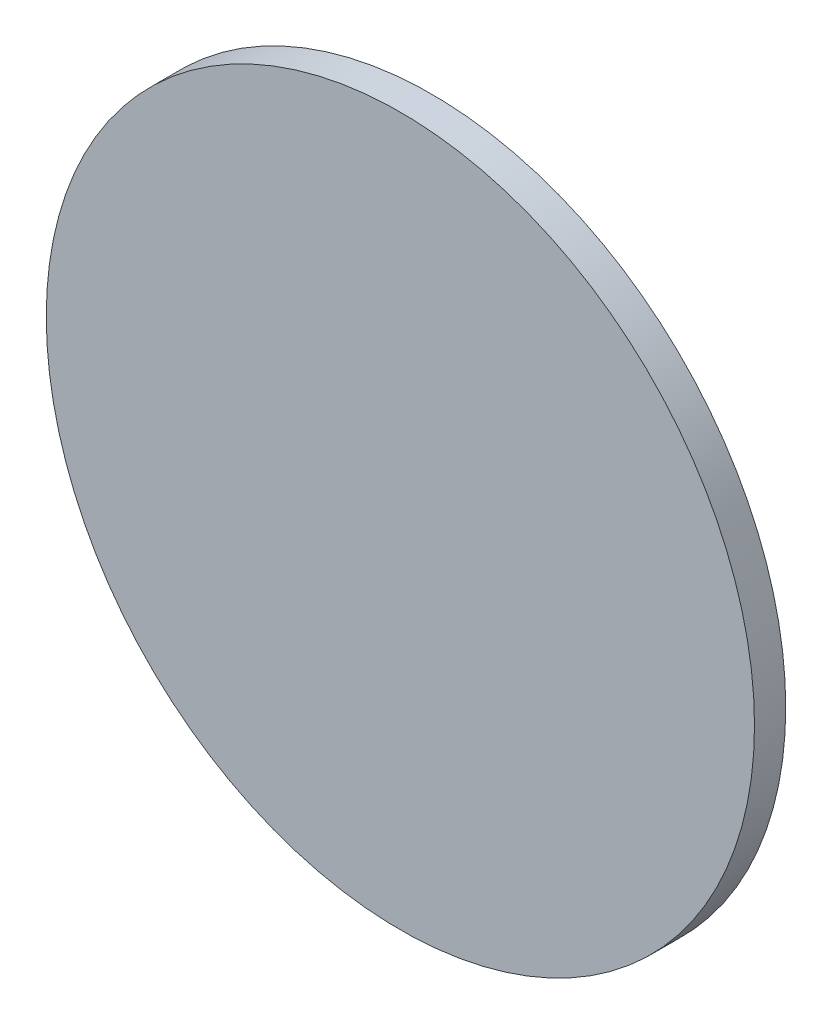
SolidWorks part; units mm, degrees
ref_plane "Front Plane" through (0, 0, 0) normal (0, 0, 1) x (1, 0, 0)
ref_plane "Top Plane" through (0, 0, 0) normal (0, 1, 0) x (1, 0, 0)
ref_plane "Right Plane" through (0, 0, 0) normal (1, 0, 0) x (0, 0, -1)
sketch "Sketch1" plane through (0, 0, 0) normal (0, 0, 1) x (1, 0, 0)
  circle A0 centre (0, 0) radius 85
  dimension "D1" = 170
extrude "Boss-Extrude1" add sketch "Sketch1" along normal blind 7.5
sketch "Sketch3" plane through (0, 0, -92.825) normal (-0.8372, -0.5469, 0) x (0, 0, -1)
  line L0 (-92.825, 0) -> (-92.825, 85) construction
  line L1 (-92.825, 85) -> (-92.825, 80) construction
  line L2 (-92.825, 82) -> (-92.825, 78)
  line L3 (-92.825, 80) -> (-94.825, 80) construction
  line L4 (-92.825, -85) -> (-92.825, 85) construction
  arc A0 (-92.825, 82) -> (-92.825, 78) centre (-92.825, 80) ccw
  dimension "D2" = 2
  dimension "D1" = 5
extrude "Cut-Extrude1" cut sketch "Sketch3" against normal blind 2 and the other way blind 2
sketch "Sketch4" plane through (0, 0, -92.825) normal (-0.8372, -0.5469, 0) x (0, 0, -1)
  circle A0 centre (-92.825, 80) radius 1
  dimension "D1" = 2
extrude "Boss-Extrude2" add sketch "Sketch4" along normal blind 2 and the other way blind 2
sketch "Sketch5" plane through (-1.6743, -1.0939, 0) normal (-0.8372, -0.5469, 0) x (0, 0, -1)
  line L0 (0, 79) -> (0, 81) construction
  line L1 (0, 81) -> (0, 79)
  arc A0 (0, 81) -> (0, 79) centre (0, 80) cw
revolve "Revolve1" add sketch "Sketch5" angle 90 about L1 region at (42.0812, -68.0674, -0.4244)
ref_plane "Plane1" through (0, 0, 0) normal (0.8372, 0.5469, 0) x (0, 0, -1)
mirror "Mirror1" about plane through (0, 0, 0) normal (0.8372, 0.5469, 0) of "Revolve1"
pattern_circular "CirPattern1" count 3 over 360 about axis through (0, 0, 7.5) along (0, 0, -1) of "Cut-Extrude1", "Boss-Extrude2", "Revolve1", "Mirror1"
sketch "Sketch6" plane through (0, 0, 0) normal (1, 0, 0) x (0, 0, -1)
  line L0 (5, 0) -> (-5, 0)
  arc A0 (5, 0) -> (-5, 0) centre (0, 0) ccw
  dimension "D1" = 10
revolve "Cut-Revolve1" cut sketch "Sketch6" angle 360 about L0
